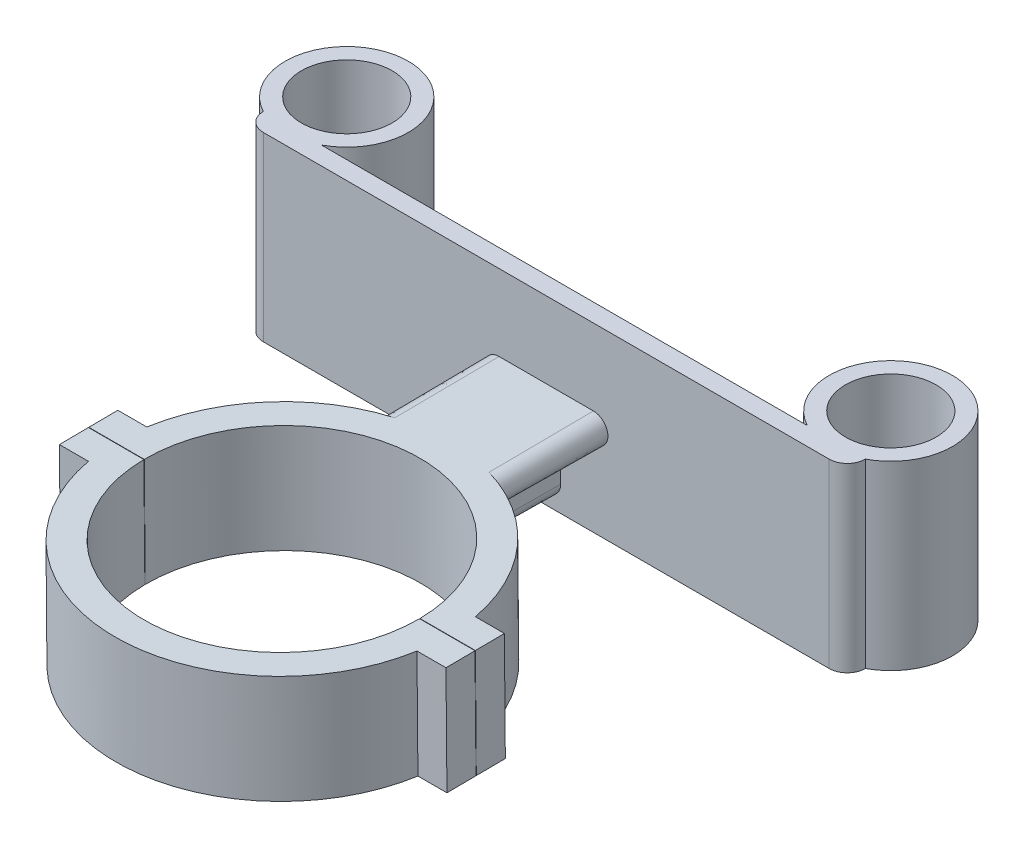
SolidWorks part; units mm, degrees
material "Полиэтилен ВД ГОСТ 16337-77"
ref_plane "Спереди" through (0, 0, 0) normal (0, 0, 1) x (1, 0, 0)
ref_plane "Сверху" through (0, 0, 0) normal (0, 1, 0) x (1, 0, 0)
ref_plane "Справа" through (0, 0, 0) normal (1, 0, 0) x (0, 0, -1)
ref_axis "ОсьX" through (-88.99, 0, 0) along (1, 0, 0)
ref_axis "ОсьZ" through (0, 55, 0) along (0, -1, 0)
ref_axis "ОсьY" through (0, 0, -88.99) along (0, 0, 1)
sketch "Эскиз1" plane through (0, 0, 0) normal (0, 0, 1) x (1, 0, 0)
  line L0 (-13.7709, 0) -> (0, 0) construction
  line L1 (-83, 25) -> (83, 25)
  line L2 (-83, 25) -> (-83, -25)
  line L3 (-83, -25) -> (83, -25)
  line L4 (83, 25) -> (83, -25)
  line L5 (0, 0) -> (0, 15.6102) construction
  point P4 (-83, 0)
  point P6 (0, 25)
  dimension "D1" = 166
  dimension "D2" = 50
extrude "Бобышка-Вытянуть1" add sketch "Эскиз1" along normal blind 5
sketch "Эскиз4" plane through (0, 0, 0) normal (0, 1, 0) x (1, 0, 0)
  line L0 (0, -3.31) -> (0, 24.236) construction
  line L1 (-83, 0) -> (-67, 0)
  line L2 (83, 0) -> (-83, 0) construction
  line L3 (83, 0) -> (67, 0)
  circle A0 centre (-75, 15) radius 12.5
  arc A1 (-67, 0) -> (-83, 0) centre (-75, 15) ccw
  arc A2 (67, 0) -> (83, 0) centre (75, 15) cw
  circle A3 centre (75, 15) radius 12.5
  dimension "D1" = 25
  dimension "D2" = 17
  dimension "D3" = 15
  dimension "D4" = 150
extrude "Бобышка-Вытянуть4" add sketch "Эскиз4" along normal up to surface and the other way up to surface up to face at (0, 25, 2.5) other way up to face at (0, -25, 2.5)
fillet "Скругление1" radius 5 2 edges at (83, 0, 5) (-83, 0, 5)
sketch "Эскиз2" plane through (0, 0, 5) normal (0, 0, 1) x (1, 0, 0)
  line L0 (-13, 0) -> (13, 0) construction
  line L1 (-13, 4) -> (13, 4)
  line L2 (-13, -4) -> (-5, -4)
  line L3 (0, -4) -> (0, -18) construction
  line L4 (4, -5) -> (4, -18)
  line L5 (-4, -5) -> (-4, -18)
  line L6 (5, -4) -> (13, -4)
  arc A0 (-13, 4) -> (-13, -4) centre (-13, 0) ccw
  arc A1 (13, -4) -> (13, 4) centre (13, 0) ccw
  arc A3 (-4, -18) -> (4, -18) centre (0, -18) ccw
  arc A4 (4, -5) -> (5, -4) centre (5, -5) cw
  arc A5 (-4, -5) -> (-5, -4) centre (-5, -5) ccw
  point P2 (0, 0)
  point P7 (0, -7.5)
  dimension "D2" = 30
  dimension "D3" = 22
  dimension "D4" = 1
  dimension "D1" = 8
extrude "Бобышка-Вытянуть2" add sketch "Эскиз2" along normal blind 30 draft 0.5
sketch "Эскиз3" plane through (0, 4.0433, 0.0353) normal (0, 1, 0.0087) x (1, 0, 0)
  line L0 (38, -77.7953) -> (53.2901, -77.7953)
  line L1 (-53.2901, -77.7953) -> (-38, -77.7953)
  line L3 (-53.2901, -77.8953) -> (-38, -77.8953)
  line L5 (38, -77.8953) -> (53.2901, -77.8953)
  line L6 (-13.7929, -77.8453) -> (8.3285, -77.8453) construction
  line L8 (-53.2901, -77.7953) -> (-53.2901, -69.7953)
  line L9 (-53.2901, -69.7953) -> (-45.2901, -69.7953)
  line L10 (0, -77.8453) -> (0, -255.6089) construction
  line L11 (-53.2901, -77.8953) -> (-53.2901, -85.8953)
  line L12 (-53.2901, -85.8953) -> (-45.2901, -85.8953)
  line L13 (53.2901, -85.8953) -> (45.2901, -85.8953)
  line L14 (53.2901, -77.8953) -> (53.2901, -85.8953)
  line L15 (53.2901, -77.7953) -> (53.2901, -69.7953)
  line L16 (53.2901, -69.7953) -> (45.2901, -69.7953)
  arc A0 (-45.2901, -85.8953) -> (45.2901, -85.8953) centre (0, -77.8453) ccw
  arc A1 (-38, -77.8953) -> (38, -77.8953) centre (0, -77.8453) ccw
  arc A2 (38, -77.7953) -> (-38, -77.7953) centre (0, -77.8453) ccw
  circle A3 centre (0, -77.8453) radius 46 construction
  circle A4 centre (0, -77.8453) radius 38 construction
  arc A5 (45.2901, -69.7953) -> (-45.2901, -69.7953) centre (0, -77.8453) ccw
  point P1 (36.3396, -238.7245)
  point P9 (43.99, -236.3855)
  dimension "D2" = 76
  dimension "D3" = 0.1
  dimension "D4" = 8
  dimension "D5" = 8
  dimension "D1" = 8
extrude "Бобышка-Вытянуть3" add sketch "Эскиз3" against normal blind 30
